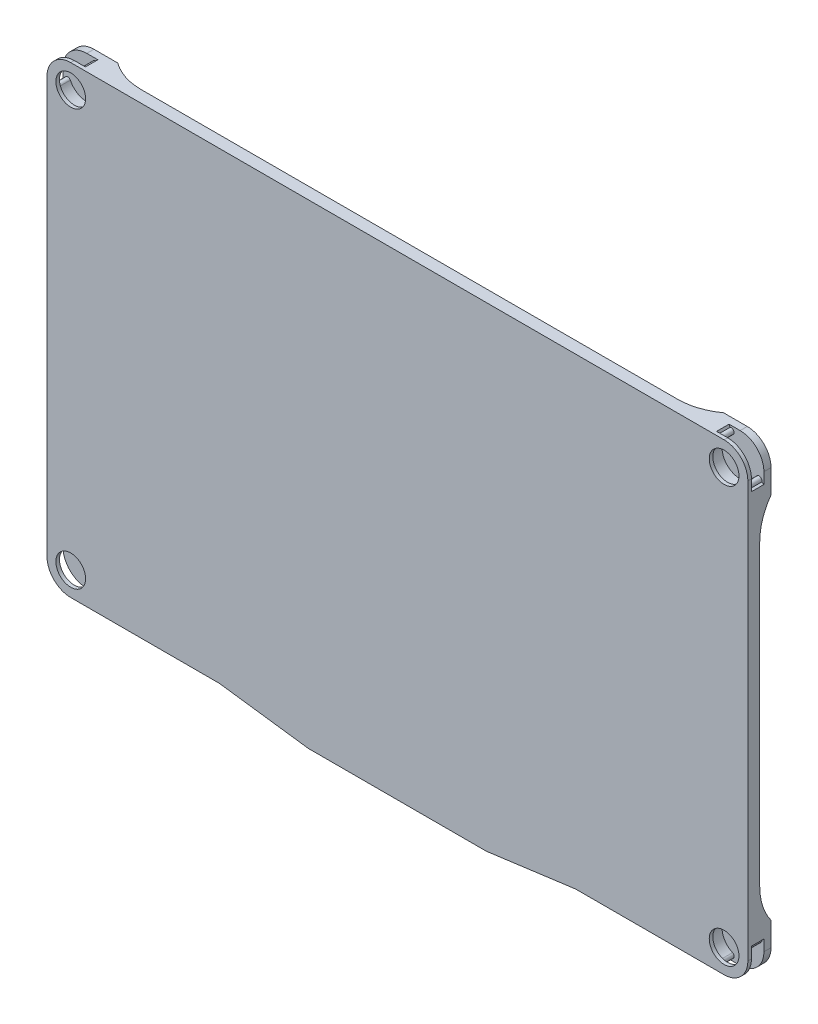
SolidWorks part; units mm, degrees
ref_plane "前视基准面" through (0, 0, 0) normal (0, 0, 1) x (1, 0, 0)
ref_plane "上视基准面" through (0, 0, 0) normal (0, 1, 0) x (1, 0, 0)
ref_plane "右视基准面" through (0, 0, 0) normal (1, 0, 0) x (0, 0, -1)
sketch "草图1" plane through (0, 0, 0) normal (0, 0, 1) x (1, 0, 0)
  line L0 (0, 69.3683) -> (0, -65.8356) construction
  line L1 (-55, -39) -> (-30, -39)
  line L2 (-59, -35) -> (-59, 35)
  line L3 (-55, 39) -> (55, 39)
  line L4 (59, -35) -> (59, 35)
  line L5 (-59, -39) -> (59, 39) construction
  line L6 (-59, 39) -> (59, -39) construction
  line L7 (30, -39) -> (15, -41)
  line L8 (15, -41) -> (-15, -41)
  line L9 (-30, -39) -> (-15, -41)
  line L10 (30, -39) -> (55, -39)
  arc A0 (-59, 35) -> (-55, 39) centre (-55, 35) cw
  arc A1 (-55, -39) -> (-59, -35) centre (-55, -35) cw
  arc A2 (55, -39) -> (59, -35) centre (55, -35) ccw
  arc A3 (55, 39) -> (59, 35) centre (55, 35) cw
  point P0 (0, 0)
  point P25 (0, -41)
  dimension "D3" = 4
  dimension "D1" = 118
  dimension "D2" = 78
  dimension "D4" = 2
  dimension "D5" = 30
  dimension "D6" = 60
extrude "凸台-拉伸1" add sketch "草图1" along normal blind 3.9
sketch "草图2" plane through (0, 0, 3.9) normal (0, 0, 1) x (1, 0, 0)
  line L0 (0, 54.7276) -> (0, -53.7782) construction
  line L1 (-66.26, 0) -> (70.6309, 0) construction
  circle A0 centre (55, 35) radius 2.5
  circle A1 centre (-55, 35) radius 2.5
  circle A2 centre (55, -35) radius 2.5
  circle A3 centre (-55, -35) radius 2.5
  dimension "D1" = 5
extrude "切除-拉伸1" cut sketch "草图2" against normal blind 0.6
sketch "草图3" plane through (0, 0, 3.3) normal (0, 0, 1) x (1, 0, 0)
  line L0 (55, 35) -> (56.7426, 36.7426) construction
  line L1 (55, 35) -> (55.654, 35) construction
  line L2 (53.5103, 38.1947) -> (55, 35) construction
  line L3 (53.3095, 38.6252) -> (52.8869, 39.5315)
  line L4 (58.6252, 33.3095) -> (59.5315, 32.8869)
  line L5 (0, 50.3598) -> (0, -52.386) construction
  line L6 (-66.2421, 0) -> (66.138, 0) construction
  line L7 (-53.5103, 38.1947) -> (-55, 35) construction
  line L8 (-55, 35) -> (-55.654, 35) construction
  line L9 (-55, 35) -> (-56.7426, 36.7426) construction
  line L10 (-58.6252, 33.3095) -> (-59.5315, 32.8869)
  line L11 (-53.3095, 38.6252) -> (-52.8869, 39.5315)
  line L12 (-55, -35) -> (-56.7426, -36.7426) construction
  line L13 (-55, -35) -> (-55.654, -35) construction
  line L14 (-53.5103, -38.1947) -> (-55, -35) construction
  line L15 (53.5103, -38.1947) -> (55, -35) construction
  line L16 (55, -35) -> (55.654, -35) construction
  line L17 (55, -35) -> (56.7426, -36.7426) construction
  line L18 (-53.3095, -38.6252) -> (-52.8869, -39.5315)
  line L19 (-58.6252, -33.3095) -> (-59.5315, -32.8869)
  line L20 (58.6252, -33.3095) -> (59.5315, -32.8869)
  line L21 (53.3095, -38.6252) -> (52.8869, -39.5315)
  arc A0 (53.711, 37.7642) -> (57.7642, 33.711) centre (55, 35) ccw
  arc A1 (53.711, 37.7642) -> (53.3095, 38.6252) centre (53.5103, 38.1947) ccw
  arc A2 (57.7642, 33.711) -> (58.6252, 33.3095) centre (58.1947, 33.5103) cw
  circle A3 centre (55, 35) radius 4 construction
  arc A4 (59.5315, 32.8869) -> (52.8869, 39.5315) centre (55, 35) ccw
  circle A5 centre (-55, 35) radius 4 construction
  arc A6 (-59.5315, 32.8869) -> (-52.8869, 39.5315) centre (-55, 35) cw
  arc A7 (-57.7642, 33.711) -> (-58.6252, 33.3095) centre (-58.1947, 33.5103) ccw
  arc A8 (-53.711, 37.7642) -> (-53.3095, 38.6252) centre (-53.5103, 38.1947) cw
  arc A9 (-53.711, 37.7642) -> (-57.7642, 33.711) centre (-55, 35) cw
  circle A10 centre (-55, -35) radius 4 construction
  circle A11 centre (55, -35) radius 4 construction
  arc A12 (-53.711, -37.7642) -> (-57.7642, -33.711) centre (-55, -35) ccw
  arc A13 (-53.711, -37.7642) -> (-53.3095, -38.6252) centre (-53.5103, -38.1947) ccw
  arc A14 (-57.7642, -33.711) -> (-58.6252, -33.3095) centre (-58.1947, -33.5103) cw
  arc A15 (-59.5315, -32.8869) -> (-52.8869, -39.5315) centre (-55, -35) ccw
  arc A16 (59.5315, -32.8869) -> (52.8869, -39.5315) centre (55, -35) cw
  arc A17 (57.7642, -33.711) -> (58.6252, -33.3095) centre (58.1947, -33.5103) ccw
  arc A18 (53.711, -37.7642) -> (53.3095, -38.6252) centre (53.5103, -38.1947) cw
  arc A19 (53.711, -37.7642) -> (57.7642, -33.711) centre (55, -35) cw
  point P13 (55, 35)
  point P31 (-55, 35)
  point P56 (-55, -35)
  point P57 (55, -35)
  dimension "D1" = 6.1
  dimension "D4" = 10
  dimension "D5" = 8
  dimension "D2" = 45
  dimension "D3" = 70
extrude "切除-拉伸2" cut sketch "草图3" against normal blind 2.1
sketch "草图5" plane through (0, 0, 0) normal (0, 0, -1) x (-1, 0, 0)
  line L0 (-51, 35) -> (-51, 39)
  line L1 (-55, 31) -> (-59, 31)
  line L2 (0, 44.4785) -> (0, -8.6861) construction
  line L3 (51, 35) -> (51, 39)
  line L4 (55, 31) -> (59, 31)
  line L5 (-6.1645, 0) -> (76.6043, 0) construction
  line L6 (55, -31) -> (59, -31)
  line L7 (51, -35) -> (51, -39)
  line L8 (-59, 31) -> (-59, -31)
  line L9 (-51, -39) -> (-30, -39)
  line L10 (-30, -39) -> (-15, -41)
  line L11 (-15, -41) -> (15, -41)
  line L12 (15, -41) -> (30, -39)
  line L13 (30, -39) -> (51, -39)
  line L14 (59, -31) -> (59, 31)
  line L15 (51, 39) -> (-51, 39)
  line L16 (-51, -35) -> (-51, -39)
  line L17 (-55, -31) -> (-59, -31)
  arc A0 (-55, 31) -> (-51, 35) centre (-55, 35) ccw
  arc A1 (55, 31) -> (51, 35) centre (55, 35) cw
  arc A2 (55, -31) -> (51, -35) centre (55, -35) ccw
  arc A3 (-55, -31) -> (-51, -35) centre (-55, -35) cw
  point P28 (76.6043, 0)
  point P29 (0, 0)
extrude "切除-拉伸4" cut sketch "草图5" against normal blind 1.9
fillet "圆角2" radius 10 12 edges at (-57, -31, 1.9) (-52.1716, -32.1716, 1.9) (-51, 37, 1.9) (-52.1716, 32.1716, 1.9) (57, -31, 1.9) (52.1716, -32.1716, 1.9) (51, 37, 1.9) (57, 31, 1.9) (-51, -37, 1.9) (-57, 31, 1.9) (51, -37, 1.9) (52.1716, 32.1716, 1.9)
